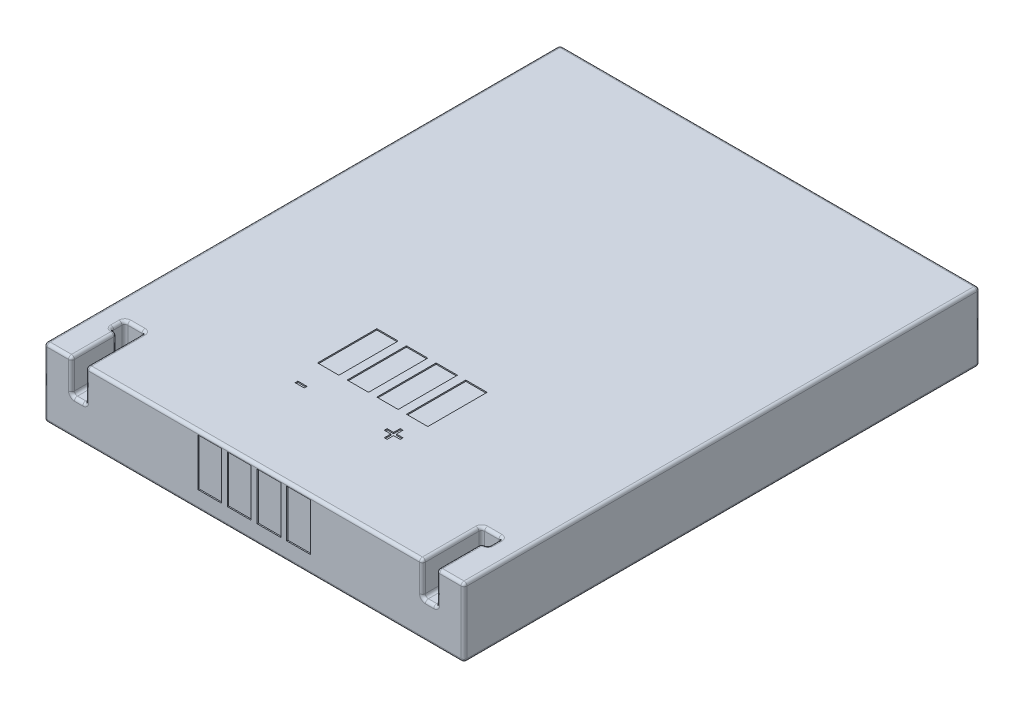
SolidWorks part; units mm, degrees
material "Custom Plastic"
ref_plane "Front Plane" through (0, 0, 0) normal (0, 0, 1) x (1, 0, 0)
ref_plane "Top Plane" through (0, 0, 0) normal (0, 1, 0) x (1, 0, 0)
ref_plane "Right Plane" through (0, 0, 0) normal (1, 0, 0) x (0, 0, -1)
sketch "Sketch1" plane through (0, 0, 0) normal (0, 1, 0) x (1, 0, 0)
  line L0 (-17.7, -21.75) -> (17.7, 21.75) construction
  line L1 (-17.7, 21.75) -> (17.7, 21.75)
  line L2 (-17.7, 21.75) -> (-17.7, -21.75)
  line L3 (-17.7, -21.75) -> (17.7, -21.75)
  line L4 (17.7, 21.75) -> (17.7, -21.75)
  dimension "D1" = 43.5
  dimension "D2" = 35.4
extrude "Boss-Extrude1" add sketch "Sketch1" along normal mid plane 5.8
sketch "Sketch2" plane through (0, 2.9, 0) normal (0, 1, 0) x (1, 0, 0)
  line L0 (0, -21.75) -> (0, -11.3418) construction
  line L1 (-17.7, -21.75) -> (17.7, -21.75) construction
  line L2 (-14.2, -21.75) -> (-14.2, -16.75)
  line L3 (-14.2, -16.75) -> (-15.9, -16.75)
  line L4 (-15.9, -16.75) -> (-15.9, -17.95)
  line L5 (-15.9, -17.95) -> (-15.4, -17.95)
  line L6 (-15.4, -17.95) -> (-15.4, -21.75)
  line L7 (-15.4, -21.75) -> (-14.2, -21.75)
  line L8 (-14.8, -21.75) -> (-14.8, -26.5691) construction
  line L9 (15.4, -21.75) -> (14.2, -21.75)
  line L10 (15.4, -17.95) -> (15.4, -21.75)
  line L11 (15.9, -17.95) -> (15.4, -17.95)
  line L12 (15.9, -16.75) -> (15.9, -17.95)
  line L13 (14.2, -16.75) -> (15.9, -16.75)
  line L14 (14.2, -21.75) -> (14.2, -16.75)
  dimension "D1" = 5
  dimension "D2" = 1.2
  dimension "D3" = 1.2
  dimension "D4" = 1.7
  dimension "D5" = 14.8
extrude "Cut-Extrude1" cut sketch "Sketch2" against normal blind 2.8
sketch "Sketch3" plane through (0, 2.9, 0) normal (0, 1, 0) x (1, 0, 0)
  line L0 (-17.7, -21.75) -> (-15.4, -21.75) construction
  line L1 (-4.65, -6.75) -> (-2.85, -6.75)
  line L2 (-4.65, -6.75) -> (-4.65, -11.75)
  line L3 (-4.65, -11.75) -> (-2.85, -11.75)
  line L4 (-2.85, -6.75) -> (-2.85, -11.75)
  line L5 (-2.15, -6.75) -> (-0.35, -6.75)
  line L6 (-2.15, -6.75) -> (-2.15, -11.75)
  line L7 (-2.15, -11.75) -> (-0.35, -11.75)
  line L8 (-0.35, -6.75) -> (-0.35, -11.75)
  line L9 (0.35, -6.75) -> (2.15, -6.75)
  line L10 (0.35, -6.75) -> (0.35, -11.75)
  line L11 (0.35, -11.75) -> (2.15, -11.75)
  line L12 (2.15, -6.75) -> (2.15, -11.75)
  line L13 (2.85, -6.75) -> (4.65, -6.75)
  line L14 (2.85, -6.75) -> (2.85, -11.75)
  line L15 (2.85, -11.75) -> (4.65, -11.75)
  line L16 (4.65, -6.75) -> (4.65, -11.75)
  line L17 (-3.75, -6.75) -> (-3.75, -4.6418) construction
  line L18 (-1.25, -6.75) -> (-1.25, -4.6418) construction
  line L19 (1.25, -6.75) -> (1.25, -4.6418) construction
  line L20 (3.75, -6.75) -> (3.75, -4.6418) construction
  line L21 (-4.65, -14.75) -> (-2.85, -14.75) construction
  line L22 (2.85, -14.75) -> (4.65, -14.75) construction
  text T0 "-"
  text T1 "+"
  dimension "D1" = 5
  dimension "D2" = 10
  dimension "D3" = 1.8
  dimension "D4" = 2.5
  dimension "D5" = 2.5
  dimension "D6" = 2.5
  dimension "D7" = 1.25
  dimension "D8" = 3
extrude "Cut-Extrude2" cut sketch "Sketch3" against normal blind 0.1
sketch "Sketch4" plane through (0, 0, 21.75) normal (0, 0, 1) x (1, 0, 0)
  line L0 (-14.2, 2.9) -> (14.2, 2.9) construction
  line L1 (-4.75, 2.6) -> (-2.75, 2.6)
  line L2 (-4.75, 2.6) -> (-4.75, -1.4)
  line L3 (-4.75, -1.4) -> (-2.75, -1.4)
  line L4 (-2.75, 2.6) -> (-2.75, -1.4)
  line L5 (-2.25, 2.6) -> (-0.25, 2.6)
  line L6 (-2.25, 2.6) -> (-2.25, -1.4)
  line L7 (-2.25, -1.4) -> (-0.25, -1.4)
  line L8 (-0.25, 2.6) -> (-0.25, -1.4)
  line L9 (0.25, 2.6) -> (2.25, 2.6)
  line L10 (0.25, 2.6) -> (0.25, -1.4)
  line L11 (0.25, -1.4) -> (2.25, -1.4)
  line L12 (2.25, 2.6) -> (2.25, -1.4)
  line L13 (2.75, 2.6) -> (4.75, 2.6)
  line L14 (2.75, 2.6) -> (2.75, -1.4)
  line L15 (2.75, -1.4) -> (4.75, -1.4)
  line L16 (4.75, 2.6) -> (4.75, -1.4)
  line L17 (-3.75, 2.6) -> (-3.75, 4.1802) construction
  line L18 (-1.25, 2.6) -> (-1.25, 4.0058) construction
  line L19 (1.25, 2.6) -> (1.25, 3.7659) construction
  line L20 (3.75, 2.6) -> (3.75, 3.7659) construction
  dimension "D1" = 2
  dimension "D2" = 4
  dimension "D3" = 0.3
  dimension "D4" = 1.25
  dimension "D5" = 2.5
  dimension "D6" = 2.5
  dimension "D7" = 2.5
extrude "Cut-Extrude3" cut sketch "Sketch4" against normal blind 0.1
fillet "Fillet1" radius 0.25 44 edges at (14.8, 0.1, 21.75) (-14.8, 0.1, 21.75) (-17.7, 2.9, 0) (-17.7, 0, 21.75) (17.7, 0, 21.75) (17.7, 2.9, 0) (17.7, 0, -21.75) (0, 2.9, -21.75) (-17.7, 0, -21.75) (0, -2.9, 21.75) (17.7, -2.9, 0) (0, -2.9, -21.75) (-17.7, -2.9, 0) (-15.9, 0.1, 17.35) (-15.9, 2.9, 17.35) (15.9, 0.1, 17.35) (15.9, 2.9, 17.35) (15.4, 1.5, 21.75) (15.4, 0.1, 19.85) (15.4, 2.9, 19.85) (15.4, 1.5, 17.95) (15.9, 1.5, 17.95) (15.9, 1.5, 16.75) (15.05, 0.1, 16.75) (15.05, 2.9, 16.75) (14.2, 1.5, 16.75) (14.2, 0.1, 19.25) (14.2, 1.5, 21.75) (14.2, 2.9, 19.25) (-14.2, 1.5, 21.75) (-14.2, 0.1, 19.25) (-14.2, 2.9, 19.25) (-15.9, 1.5, 17.95) (-14.2, 1.5, 16.75) (-15.05, 0.1, 16.75) (-15.9, 1.5, 16.75) (-15.05, 2.9, 16.75) (-15.4, 1.5, 17.95) (-15.4, 0.1, 19.85) (-15.4, 1.5, 21.75) (-15.4, 2.9, 19.85) (0, 2.9, 21.75) (16.55, 2.9, 21.75) (-16.55, 2.9, 21.75)
